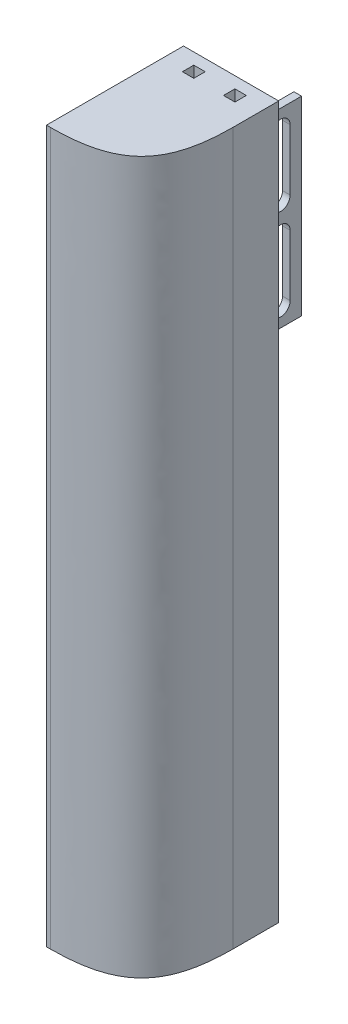
SolidWorks part; units mm, degrees
ref_plane "Front Plane" through (0, 0, 0) normal (0, 0, 1) x (1, 0, 0)
ref_plane "Top Plane" through (0, 0, 0) normal (0, 1, 0) x (1, 0, 0)
ref_plane "Right Plane" through (0, 0, 0) normal (1, 0, 0) x (0, 0, -1)
sketch "Sketch1" plane through (0, 0, 0) normal (0, 1, 0) x (1, 0, 0)
  line L1 (0, 0) -> (25, 0)
  line L2 (0, 0) -> (0, 36)
  line L3 (0, 36) -> (25, 36)
  line L4 (25, 0) -> (25, 36)
  dimension "D1" = 36
  dimension "D2" = 25
extrude "Boss-Extrude1" add sketch "Sketch1" along normal blind 186.9
fillet "Fillet1" radius 24 1 edges at (25, 93.45, 0) conic rho 0.55
sketch "Sketch2" plane through (0, 0, 0) normal (-1, 0, 0) x (0, 0, 1)
  line L0 (-24, 0) -> (0, 0) construction
  line L1 (-6.2, 83.2) -> (-1.2, 83.2)
  line L2 (-6.2, 83.2) -> (-6.2, 73.2)
  line L3 (-6.2, 73.2) -> (-1.2, 73.2)
  line L4 (-1.2, 83.2) -> (-1.2, 73.2)
  line L5 (0, 186.9) -> (0, 0) construction
  dimension "D1" = 73.2
  dimension "D2" = 1.2
  dimension "D3" = 5
  dimension "D4" = 10
extrude "Cut-Extrude1" cut sketch "Sketch2" against normal blind 4
sketch "Sketch3" plane through (0, 0, 0) normal (-1, 0, 0) x (0, 0, 1)
  line L1 (-14, 33.2) -> (-6, 33.2)
  line L2 (-14, 33.2) -> (-14, 28)
  line L3 (-14, 28) -> (-6, 28)
  line L4 (-6, 33.2) -> (-6, 28)
  line L5 (-36, 0) -> (0, 0) construction
  line L6 (0, 186.9) -> (0, 0) construction
  line L8 (-22, 33.2) -> (-30, 33.2)
  line L9 (-22, 33.2) -> (-22, 28)
  line L10 (-22, 28) -> (-30, 28)
  line L11 (-30, 33.2) -> (-30, 28)
  line L12 (-6, 61.2) -> (-14, 61.2)
  line L13 (-6, 61.2) -> (-6, 66.8)
  line L14 (-6, 66.8) -> (-14, 66.8)
  line L15 (-14, 61.2) -> (-14, 66.8)
  line L16 (-22, 66.8) -> (-30, 66.8)
  line L17 (-22, 66.8) -> (-22, 61.2)
  line L18 (-22, 61.2) -> (-30, 61.2)
  line L19 (-30, 66.8) -> (-30, 61.2)
  dimension "D1" = 28
  dimension "D2" = 6
  dimension "D3" = 8
  dimension "D4" = 5.2
  dimension "D5" = 8
  dimension "D6" = 8
  dimension "D7" = 28
  dimension "D8" = 5.6
  dimension "D9" = 8
  dimension "D10" = 6
  dimension "D11" = 8
  dimension "D12" = 5.6
  dimension "D13" = 8
extrude "Cut-Extrude2" cut sketch "Sketch3" against normal blind 10
sketch "Sketch4" plane through (0, 0, 0) normal (-1, 0, 0) x (0, 0, 1)
  line L0 (-36, 0) -> (0, 0) construction
  line L1 (-26, 160) -> (-67, 160)
  line L2 (-26, 160) -> (-26, 110)
  line L3 (-26, 110) -> (-67, 110)
  line L4 (-67, 160) -> (-67, 110)
  line L5 (-36, 186.9) -> (-36, 0) construction
  dimension "D1" = 160
  dimension "D2" = 10
  dimension "D3" = 31
  dimension "D4" = 110
extrude "Boss-Extrude2" add sketch "Sketch4" along normal blind 2
sketch "Sketch5" plane through (-2, 0, 0) normal (-1, 0, 0) x (0, 0, 1)
  line L0 (-67, 110) -> (-26, 110) construction
  line L1 (-67, 160) -> (-67, 110) construction
  line L4 (-59, 131) -> (-59, 115)
  line L6 (-64, 131) -> (-64, 115)
  line L7 (-26, 160) -> (-67, 160) construction
  line L9 (-64, 139) -> (-64, 155)
  line L11 (-59, 139) -> (-59, 155)
  arc A0 (-64, 115) -> (-59, 115) centre (-61.5, 115) ccw
  arc A2 (-59, 131) -> (-64, 131) centre (-61.5, 131) ccw
  arc A3 (-59, 155) -> (-64, 155) centre (-61.5, 155) ccw
  arc A4 (-64, 139) -> (-59, 139) centre (-61.5, 139) ccw
  dimension "D1" = 5
  dimension "D4" = 16
  dimension "D5" = 16
  dimension "D2" = 5
  dimension "D3" = 5.5
  dimension "D6" = 5
extrude "Cut-Extrude3" cut sketch "Sketch5" against normal up to next
chamfer "Chamfer1" distance 16 angle 45 1 edges at (0, 135, -36)
sketch "Sketch6" plane through (0, 0, -36) normal (0, 0, -1) x (-1, 0, 0)
  line L0 (-25, 186.9) -> (-25, 0) construction
  line L1 (-21, 183.9) -> (-15, 183.9)
  line L2 (-21, 183.9) -> (-21, 179.9)
  line L3 (-21, 179.9) -> (-15, 179.9)
  line L4 (-15, 183.9) -> (-15, 179.9)
  line L5 (-25, 186.9) -> (0, 186.9) construction
  line L6 (-1, 186.9) -> (-25, 186.9) construction
  line L7 (-10.2, 183.9) -> (-4.2, 183.9)
  line L8 (-10.2, 183.9) -> (-10.2, 179.9)
  line L9 (-10.2, 179.9) -> (-4.2, 179.9)
  line L10 (-4.2, 183.9) -> (-4.2, 179.9)
  dimension "D1" = 4
  dimension "D2" = 4
  dimension "D3" = 3
  dimension "D4" = 6
  dimension "D5" = 6
  dimension "D6" = 4.8
  dimension "D7" = 3
extrude "Cut-Extrude4" cut sketch "Sketch6" against normal blind 9
sketch "Sketch7" plane through (0, 186.9, 0) normal (0, 1, 0) x (1, 0, 0)
  line L0 (25, 24) -> (25, 36) construction
  line L1 (19.5, 33) -> (16.5, 33)
  line L2 (19.5, 33) -> (19.5, 30)
  line L3 (19.5, 30) -> (16.5, 30)
  line L4 (16.5, 33) -> (16.5, 30)
  line L5 (25, 36) -> (0, 36) construction
  line L7 (8.7, 33) -> (5.7, 33)
  line L8 (8.7, 33) -> (8.7, 30)
  line L9 (8.7, 30) -> (5.7, 30)
  line L10 (5.7, 33) -> (5.7, 30)
  dimension "D1" = 5.5
  dimension "D2" = 3
  dimension "D3" = 3
  dimension "D4" = 3
  dimension "D5" = 3
  dimension "D6" = 3
  dimension "D7" = 3
  dimension "D8" = 7.8
extrude "Cut-Extrude5" cut sketch "Sketch7" against normal blind 10
